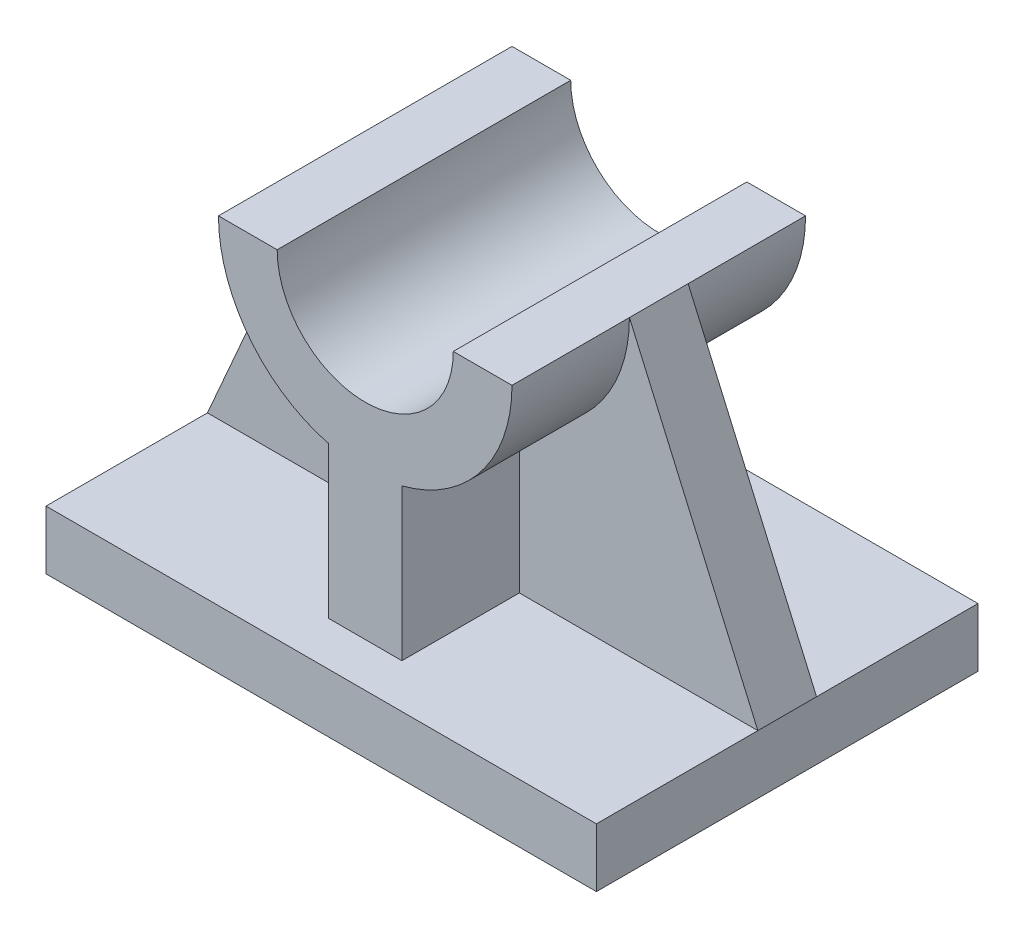
SolidWorks part; units mm, degrees
ref_plane "Front Plane" through (0, 0, 0) normal (0, 0, 1) x (1, 0, 0)
ref_plane "Top Plane" through (0, 0, 0) normal (0, 1, 0) x (1, 0, 0)
ref_plane "Right Plane" through (0, 0, 0) normal (1, 0, 0) x (0, 0, -1)
sketch "Sketch1" plane through (0, 0, 0) normal (0, 0, 1) x (1, 0, 0)
  line L0 (0, 0) -> (0, 18243.5858) construction
  line L1 (0, 0) -> (18243.5858, 0) construction
  line L2 (-20, 44) -> (-12, 44)
  line L3 (-37.5, -4) -> (37.5, -4)
  line L4 (-37.5, -4) -> (-37.5, 4)
  line L5 (-37.5, 4) -> (37.5, 4)
  line L6 (37.5, -4) -> (37.5, 4)
  line L7 (-37.5, -4) -> (37.5, 4) construction
  line L8 (-37.5, 4) -> (37.5, -4) construction
  line L10 (-5, 24.6351) -> (-5, 4)
  line L11 (-5, 4) -> (5, 4)
  line L12 (5, 24.6351) -> (5, 4)
  line L13 (12, 44) -> (20, 44)
  line L14 (-37.5, 4) -> (-20, 44)
  line L15 (37.5, 4) -> (20, 44)
  arc A0 (-20, 44) -> (20, 44) centre (0, 44) ccw
  arc A1 (-12, 44) -> (12, 44) centre (0, 44) ccw
  point P5 (0, 0)
  point P10 (0, 19)
  dimension "D1" = 12
  dimension "D2" = 20
  dimension "D3" = 10
  dimension "D4" = 40
  dimension "D5" = 8
  dimension "D6" = 75
extrude "Boss-Extrude1" add sketch "Sketch1" along normal mid plane 52 contours L3 L6 L5 L4 region at (0, 0, 0)
extrude "Boss-Extrude2" add sketch "Sketch1<3>" along normal mid plane 40 contours A0 L10 L5 L12 | A1 L2 A0 L13 region at (-16, 43.5528, 0) region at (0, 14.106, 0)
sketch "Sketch1<3>" plane through (0, 0, 0) normal (0, 0, 1) x (1, 0, 0) same geometry as "Sketch1"
extrude "Boss-Extrude3" add sketch "Sketch1<4>" along normal mid plane 8 contours A0 L12 L5 L15 | A0 L14 L5 L10 region at (-19.2178, 17.2633, 0) region at (19.2178, 17.2633, 0)
sketch "Sketch1<4>" plane through (0, 0, 0) normal (0, 0, 1) x (1, 0, 0) same geometry as "Sketch1"
